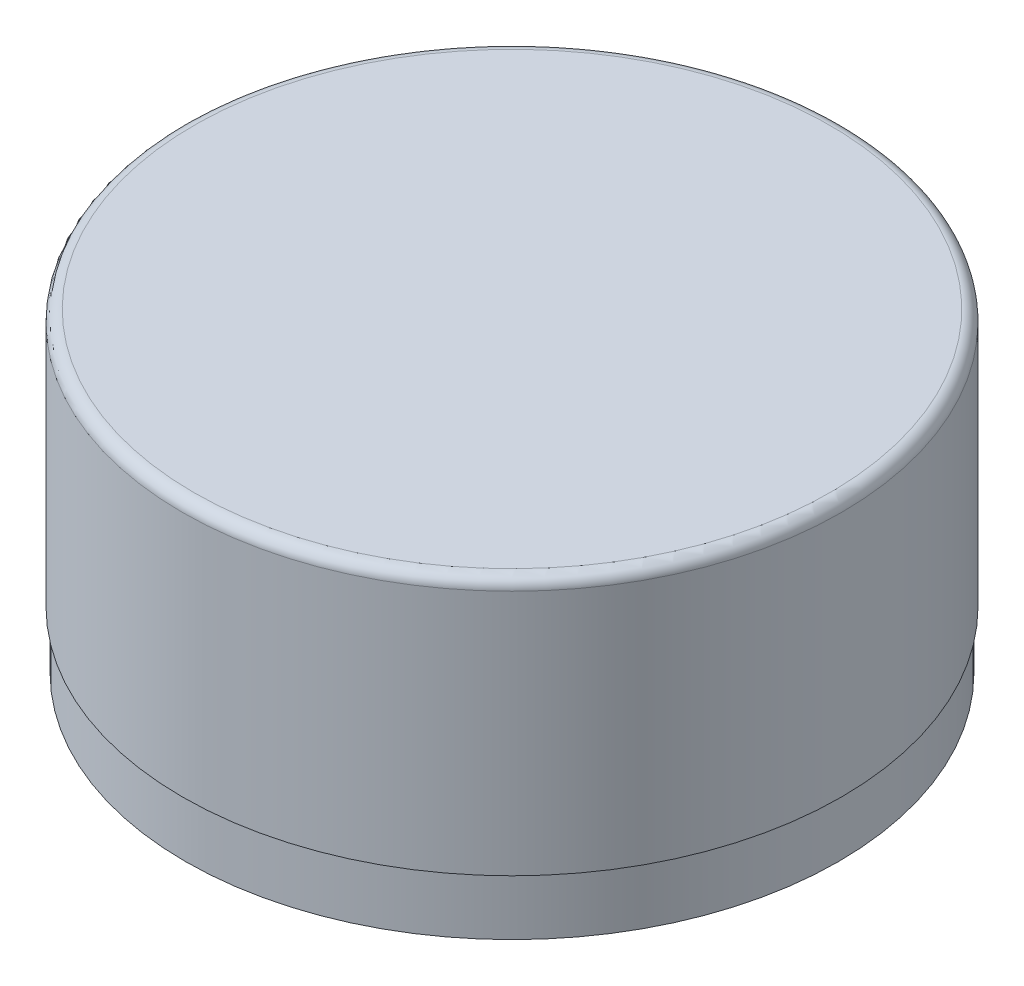
SolidWorks part; units mm, degrees
ref_plane "Front Plane" through (0, 0, 0) normal (0, 0, 1) x (1, 0, 0)
ref_plane "Top Plane" through (0, 0, 0) normal (0, 1, 0) x (1, 0, 0)
ref_plane "Right Plane" through (0, 0, 0) normal (1, 0, 0) x (0, 0, -1)
sketch "Sketch7" plane through (0, 0, 0) normal (0, 1, 0) x (1, 0, 0)
  circle A0 centre (0, 0) radius 5.7
  dimension "D1" = 11.4
extrude "Boss-Extrude2" add sketch "Sketch7" along normal blind 1
sketch "Sketch8" plane through (0, 1, 0) normal (0, 1, 0) x (1, 0, 0)
  circle A0 centre (0, 0) radius 5.75
  dimension "D1" = 11.5
extrude "Boss-Extrude3" add sketch "Sketch8" along normal blind 4.5 contours A0
fillet "Fillet4" radius 0.2 1 edges at (0, 5.5, 5.75)
sketch "Sketch9" plane through (0, 0, 0) normal (0, -1, 0) x (1, 0, 0)
  line L1 (2.5, -2.5) -> (-2.5, -2.5)
  line L2 (2.5, -2.5) -> (2.5, 2.5)
  line L3 (2.5, 2.5) -> (-2.5, 2.5)
  line L4 (-2.5, -2.5) -> (-2.5, 2.5)
  line L5 (2.5, -2.5) -> (-2.5, 2.5) construction
  line L6 (2.5, 2.5) -> (-2.5, -2.5) construction
  point P0 (0, 0)
  dimension "D1" = 5
  dimension "D2" = 5
extrude "Boss-Extrude4" add sketch "Sketch9" along normal blind 0.1 contours L3 L4 L1 L2
shell "Shell3" thickness 0.6 removed face at (0, -0.1, 0)
